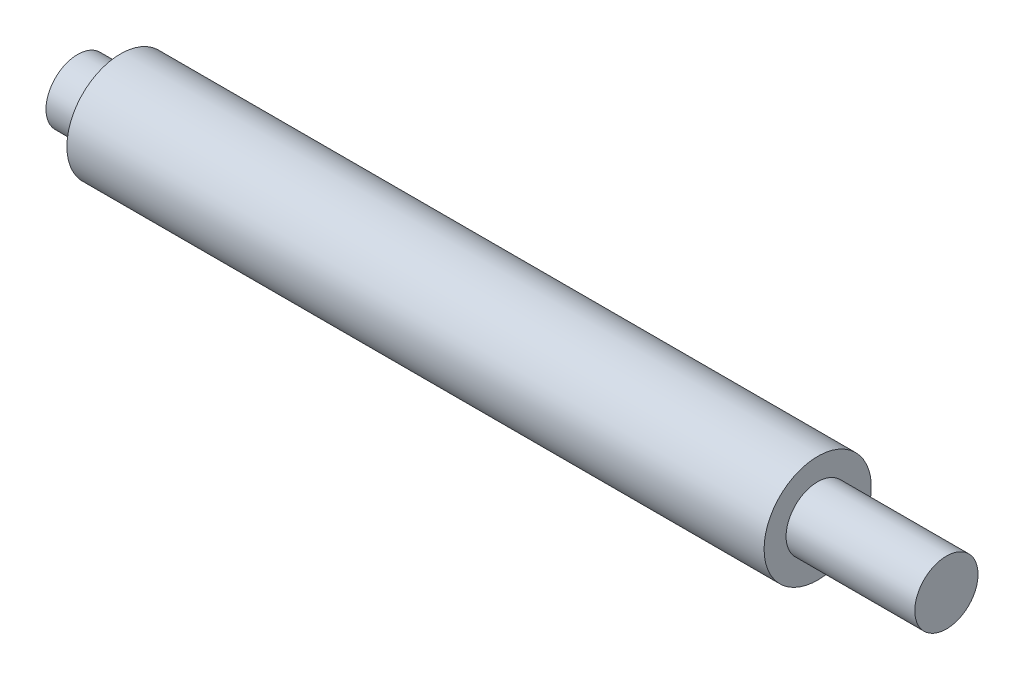
SolidWorks part; units mm, degrees
ref_plane "Front Plane" through (0, 0, 0) normal (0, 0, 1) x (1, 0, 0)
ref_plane "Top Plane" through (0, 0, 0) normal (0, 1, 0) x (1, 0, 0)
ref_plane "Right Plane" through (0, 0, 0) normal (1, 0, 0) x (0, 0, -1)
sketch "Sketch1" plane through (0, 0, 0) normal (0, 0, 1) x (1, 0, 0)
  line L0 (0, 0) -> (81, 0)
  line L1 (81, 0) -> (81, 2.95)
  line L2 (81, 2.95) -> (69, 2.95)
  line L3 (69, 2.95) -> (69, 5)
  line L4 (69, 5) -> (4, 5)
  line L5 (4, 5) -> (4, 2.95)
  line L6 (4, 2.95) -> (0, 2.95)
  line L7 (0, 2.95) -> (0, 0)
  dimension "D1" = 4
  dimension "D2" = 12
  dimension "D3" = 2.95
  dimension "D4" = 81
  dimension "D5" = 5
revolve "Revolve1" add sketch "Sketch1" angle 360 about L0
